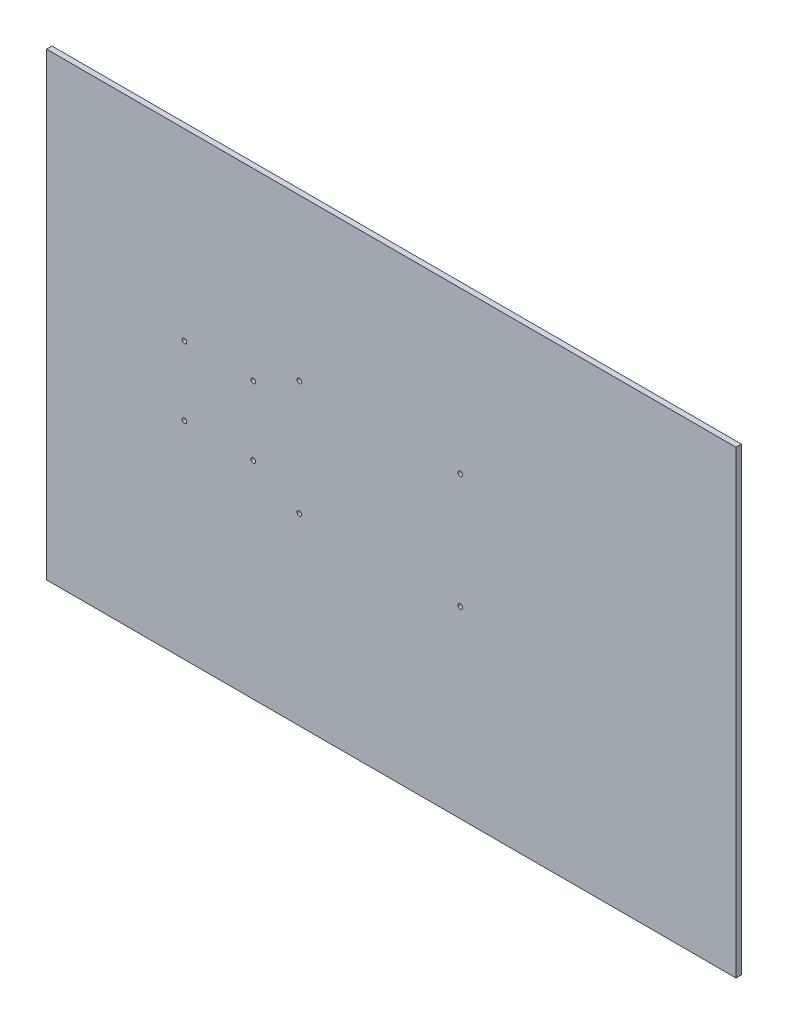
SolidWorks part; units mm, degrees
ref_plane "Front Plane" through (0, 0, 0) normal (0, 0, 1) x (1, 0, 0)
ref_plane "Top Plane" through (0, 0, 0) normal (0, 1, 0) x (1, 0, 0)
ref_plane "Right Plane" through (0, 0, 0) normal (1, 0, 0) x (0, 0, -1)
sketch "Sketch2" plane through (0, 0, 0) normal (0, 0, 1) x (1, 0, 0)
  line L0 (0, 254) -> (0, -254) construction
  line L1 (-381, -254) -> (381, -254)
  line L2 (-381, -254) -> (-381, 254)
  line L3 (-381, 254) -> (381, 254)
  line L4 (381, -254) -> (381, 254)
  line L5 (-381, -254) -> (381, 254) construction
  line L6 (-381, 254) -> (381, -254) construction
  line L7 (-304.8, 254) -> (-304.8, -254) construction
  line L8 (-355.6, 254) -> (-355.6, -254) construction
  line L9 (-330.2, 254) -> (-330.2, -254) construction
  line L10 (-279.4, 254) -> (-279.4, -254) construction
  line L11 (-254, 254) -> (-254, -254) construction
  line L12 (-228.6, 254) -> (-228.6, -254) construction
  line L13 (-203.2, 254) -> (-203.2, -254) construction
  line L14 (-177.8, 254) -> (-177.8, -254) construction
  line L15 (-152.4, 254) -> (-152.4, -254) construction
  line L16 (-127, 254) -> (-127, -254) construction
  line L17 (-101.6, 254) -> (-101.6, -254) construction
  line L18 (-76.2, 254) -> (-76.2, -254) construction
  line L19 (-50.8, 254) -> (-50.8, -254) construction
  line L20 (-25.4, 254) -> (-25.4, -254) construction
  line L21 (25.4, 254) -> (25.4, -254) construction
  line L22 (50.8, 254) -> (50.8, -254) construction
  line L23 (76.2, 254) -> (76.2, -254) construction
  line L24 (101.6, 254) -> (101.6, -254) construction
  line L25 (127, 254) -> (127, -254) construction
  line L26 (152.4, 254) -> (152.4, -254) construction
  line L27 (177.8, 254) -> (177.8, -254) construction
  line L28 (203.2, 254) -> (203.2, -254) construction
  line L29 (228.6, 254) -> (228.6, -254) construction
  line L30 (254, 254) -> (254, -254) construction
  line L31 (279.4, 254) -> (279.4, -254) construction
  line L32 (304.8, 254) -> (304.8, -254) construction
  line L33 (330.2, 254) -> (330.2, -254) construction
  line L34 (355.6, 254) -> (355.6, -254) construction
  line L35 (-381, 0) -> (381, 0) construction
  line L36 (-381, 152.4) -> (381, 152.4) construction
  line L37 (-381, 177.8) -> (381, 177.8) construction
  line L38 (-381, 203.2) -> (381, 203.2) construction
  line L39 (-381, 228.6) -> (381, 228.6) construction
  line L40 (-381, 127) -> (381, 127) construction
  line L41 (-381, 101.6) -> (381, 101.6) construction
  line L42 (-381, 76.2) -> (381, 76.2) construction
  line L43 (-381, 50.8) -> (381, 50.8) construction
  line L44 (-381, 25.4) -> (381, 25.4) construction
  line L45 (-381, -25.4) -> (381, -25.4) construction
  line L46 (-381, -50.8) -> (381, -50.8) construction
  line L47 (-381, -76.2) -> (381, -76.2) construction
  line L48 (-381, -101.6) -> (381, -101.6) construction
  line L49 (-381, -127) -> (381, -127) construction
  line L50 (-381, -152.4) -> (381, -152.4) construction
  line L51 (-381, -177.8) -> (381, -177.8) construction
  line L52 (-381, -203.2) -> (381, -203.2) construction
  line L53 (-381, -228.6) -> (381, -228.6) construction
  line L54 (-381, 12.7) -> (381, 12.7) construction
  circle A0 centre (-228.6, 50.8) radius 2.555
  circle A1 centre (-228.6, -25.4) radius 2.555
  circle A2 centre (-152.4, 50.8) radius 2.555
  circle A3 centre (-152.4, -25.4) radius 2.555
  circle A5 centre (-101.6, 76.2) radius 2.555
  circle A6 centre (-101.6, -50.8) radius 2.555
  circle A9 centre (76.2, 76.2) radius 2.555
  circle A10 centre (76.2, -50.8) radius 2.555
  point P0 (0, 0)
  dimension "D17" = 5.11
  dimension "D18" = 5.11
  dimension "D19" = 5.11
  dimension "D20" = 5.11
  dimension "D22" = 5.11
  dimension "D23" = 5.11
  dimension "D24" = 5.11
  dimension "D25" = 5.11
  dimension "D1" = 762
  dimension "D2" = 508
  dimension "D3" = 25.4
  dimension "D4" = 25.4
  dimension "D5" = 25.4
  dimension "D6" = 25.4
  dimension "D7" = 25.4
  dimension "D8" = 25.4
  dimension "D9" = 25.4
  dimension "D10" = 25.4
  dimension "D11" = 25.4
  dimension "D12" = 25.4
  dimension "D13" = 25.4
  dimension "D14" = 25.4
  dimension "D15" = 25.4
  dimension "D16" = 25.4
  dimension "D21" = 12.7
extrude "Boss-Extrude1" add sketch "Sketch2" along normal blind 6
